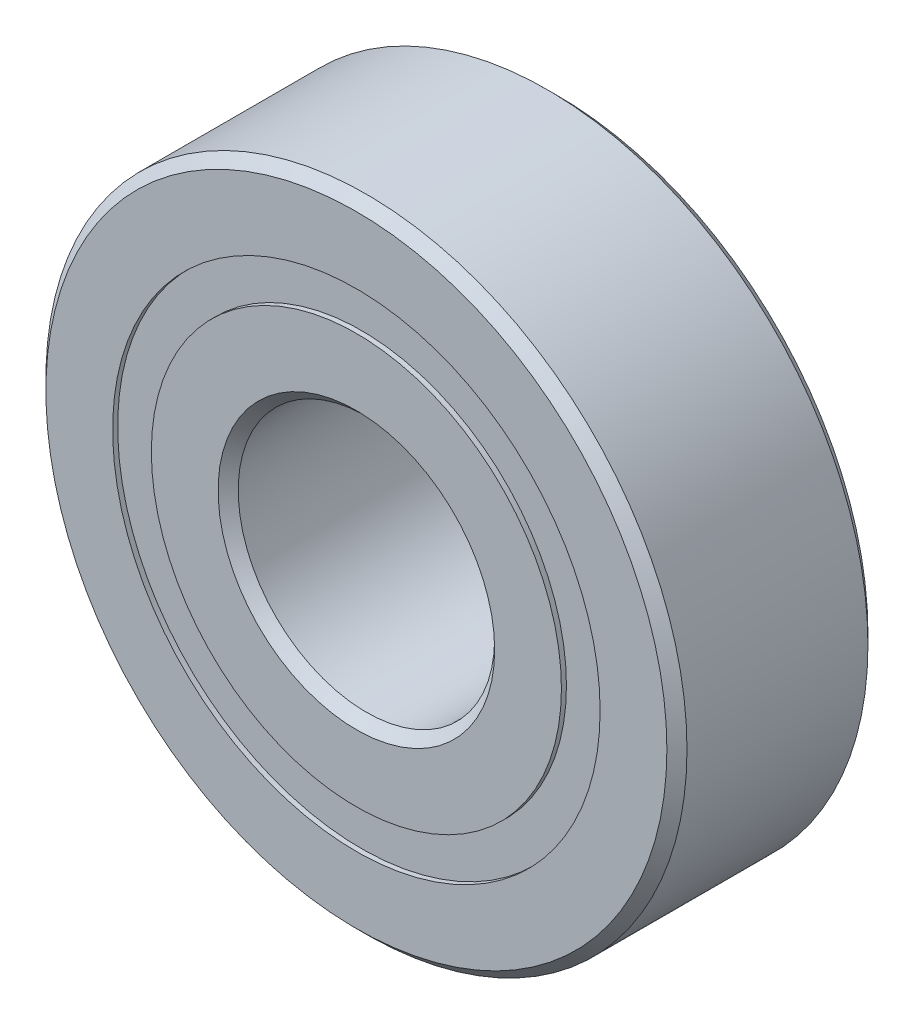
SolidWorks part; units mm, degrees
ref_plane "Front Plane" through (0, 0, 0) normal (0, 0, 1) x (1, 0, 0)
ref_plane "Top Plane" through (0, 0, 0) normal (0, 1, 0) x (1, 0, 0)
ref_plane "Right Plane" through (0, 0, 0) normal (1, 0, 0) x (0, 0, -1)
sketch "Sketch1" plane through (0, 0, 0) normal (1, 0, 0) x (0, 0, -1)
  line L0 (-2.4892, 0) -> (2.4892, 0) construction
  line L1 (0, 7.9375) -> (0, -7.9375) construction
  line L2 (2.2403, 7.9375) -> (-2.2403, 7.9375)
  line L3 (-2.2403, 7.9375) -> (-2.4892, 7.6886)
  line L4 (-2.4892, 7.6886) -> (-2.4892, 6.0352)
  line L5 (-2.4892, 6.0352) -> (-1.1063, 6.0352)
  line L6 (2.4892, 6.0352) -> (1.1063, 6.0352)
  line L7 (2.4892, 7.6886) -> (2.4892, 6.0352)
  line L8 (2.2403, 7.9375) -> (2.4892, 7.6886)
  line L9 (0, 7.9375) -> (0, 5.5563) construction
  line L10 (0, 5.5563) -> (0, 3.175) construction
  arc A0 (-1.1063, 6.0352) -> (1.1063, 6.0352) centre (0, 5.5563) cw
  point P14 (0, 3.175)
  dimension "D3" = 2.2126
  dimension "D1" = 45
  dimension "Width" = 4.9784
  dimension "OD" = 15.875
  dimension "D2" = 0.2489
  dimension "Shaft Dia" = 6.35
  dimension "D4" = 0.479
revolve "Revolve1" add sketch "Sketch1" angle 360 about L0
sketch "Sketch3" plane through (0, 0, 0) normal (1, 0, 0) x (0, 0, -1)
  line L0 (-2.4892, 5.0773) -> (-1.1063, 5.0773)
  line L1 (0, 7.9375) -> (0, -7.9375) construction
  line L2 (-2.4892, 7.6886) -> (-2.4892, 6.0352) construction
  line L3 (-2.4892, 5.0773) -> (-2.4892, 3.4239)
  line L4 (-2.2403, 7.9375) -> (-2.4892, 7.6886) construction
  line L5 (-2.4892, 3.4239) -> (-2.2403, 3.175)
  line L6 (-2.2403, 3.175) -> (2.2403, 3.175)
  line L7 (2.2403, 7.9375) -> (2.2403, -7.9375) construction
  line L8 (2.2403, 3.175) -> (2.4892, 3.4239)
  line L9 (2.4892, -7.6886) -> (2.4892, 7.6886) construction
  line L10 (2.4892, 3.4239) -> (2.4892, 5.0773)
  line L11 (2.4892, 5.0773) -> (1.1063, 5.0773)
  line L13 (2.2403, 7.9375) -> (2.4892, 7.6886) construction
  arc A0 (1.1063, 6.0352) -> (-1.1063, 6.0352) centre (0, 5.5563) ccw construction
  arc A1 (1.1063, 5.0773) -> (-1.1063, 5.0773) centre (0, 5.5562) cw
revolve "Revolve3" add sketch "Sketch3" angle 360 about L0
sketch "Sketch4" plane through (0, 0, 0) normal (1, 0, 0) x (0, 0, -1)
  line L0 (-1.2055, 5.5563) -> (1.2055, 5.5563)
  arc A2 (-1.2055, 5.5563) -> (1.2055, 5.5563) centre (0, 5.5563) cw
  arc A3 (1.1063, 6.0352) -> (-1.1063, 6.0352) centre (0, 5.5563) ccw construction
revolve "Revolve4" add sketch "Sketch4" angle 360 about L0
ref_axis "Axis1" through (0, 0, -2.4892) along (0, 0, 1)
pattern_circular "CirPattern1" count 8 every 45 about axis through (0, 0, -2.4892) along (0, 0, 1) of bodies 104
sketch "Sketch5" plane through (0, 0, 0) normal (1, 0, 0) x (0, 0, -1)
  line L0 (-2.4892, 6.0352) -> (-1.1063, 6.0352) construction
  line L1 (-2.3647, 6.0352) -> (-1.2055, 6.0352)
  line L2 (-2.3647, 6.0352) -> (-2.3647, 5.0773)
  line L3 (-2.3647, 5.0773) -> (-1.2055, 5.0773)
  line L4 (-1.2055, 6.0352) -> (-1.2055, 5.0773)
  line L5 (-2.4892, 5.0773) -> (-1.1063, 5.0773) construction
  line L6 (2.4892, 6.0352) -> (1.1063, 6.0352) construction
  line L7 (2.3647, 6.0352) -> (1.2055, 6.0352)
  line L8 (2.3647, 6.0352) -> (2.3647, 5.0773)
  line L9 (2.3647, 5.0773) -> (1.2055, 5.0773)
  line L10 (1.2055, 6.0352) -> (1.2055, 5.0773)
  line L11 (2.4892, 5.0773) -> (1.1063, 5.0773) construction
  line L12 (-2.2403, 7.9375) -> (-2.4892, 7.6886) construction
  point P18 (-2.3647, 7.813)
revolve "Revolve5" add sketch "Sketch5" angle 360 about L0
equation "\"D2@Sketch1\" = \"Width@Sketch1\"*.05"
equation "\"D3@Sketch1\" = \"Width@Sketch1\"/2.25"
equation "\"D4@Sketch1\" = (((\"OD@Sketch1\"-\"Width@Sketch1\")/2)/3.25)/3.5"
equation "\"D2@CirPattern1\" = 360/\"Balls@CirPattern1\""
